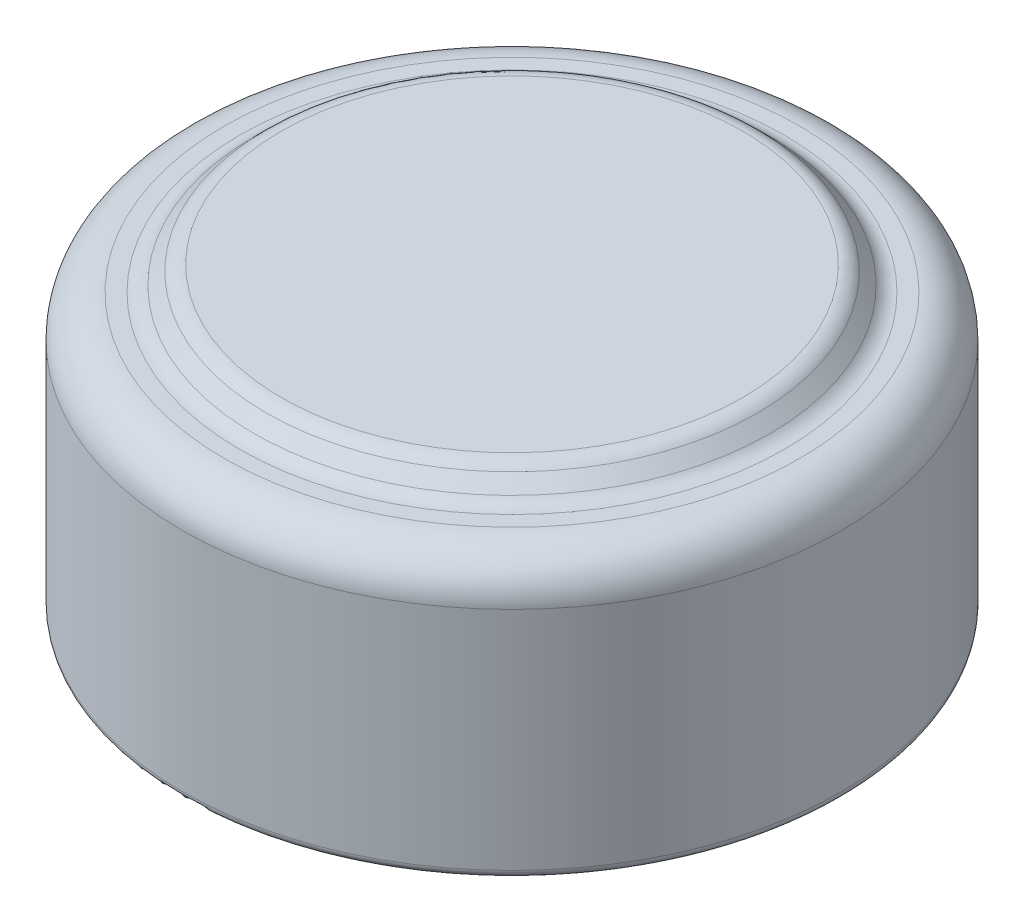
SolidWorks part; units mm, degrees
ref_plane "Front Plane" through (0, 0, 0) normal (0, 0, 1) x (1, 0, 0)
ref_plane "Top Plane" through (0, 0, 0) normal (0, 1, 0) x (1, 0, 0)
ref_plane "Right Plane" through (0, 0, 0) normal (1, 0, 0) x (0, 0, -1)
sketch "Sketch1" plane through (0, 0, 0) normal (0, 0, 1) x (1, 0, 0)
  line L0 (0, 0) -> (-3.85, 0)
  line L1 (-3.95, 0.1) -> (-3.95, 2.81)
  line L2 (0, 3.6) -> (-2.7664, 3.6)
  line L3 (0, 3.6) -> (0, 0)
  line L5 (-3.0868, 3.3832) -> (-2.9432, 3.5268)
  line L7 (-3.45, 3.31) -> (-3.2636, 3.31)
  arc A0 (-3.95, 2.81) -> (-3.45, 3.31) centre (-3.45, 2.81) cw
  arc A1 (-3.2636, 3.31) -> (-3.0868, 3.3832) centre (-3.2636, 3.56) ccw
  arc A2 (-2.7664, 3.6) -> (-2.9432, 3.5268) centre (-2.7664, 3.35) ccw
  arc A3 (-3.85, 0) -> (-3.95, 0.1) centre (-3.85, 0.1) cw
  point P9 (-3.95, 3.31)
  point P12 (-3.16, 3.31)
  point P17 (-3.95, 0)
  dimension "D6" = 0.5
  dimension "D7" = 0.25
  dimension "D8" = 0.1
  dimension "D5" = 45
  dimension "D1" = 3.95
  dimension "D2" = 3.6
  dimension "D3" = 3.16
  dimension "D4" = 3.31
revolve "Revolve1" add sketch "Sketch1" angle 360 about L3
sketch "Sketch2" plane through (0, 0, 0) normal (0, -1, 0) x (1, 0, 0)
  line L0 (0.25, -0.25) -> (0.25, -1.5)
  line L1 (-0.25, -0.25) -> (-0.25, -1.5)
  line L2 (-0.25, 1.5) -> (0.25, 1.5)
  line L3 (-0.25, 1.5) -> (-0.25, 0.25)
  line L4 (-0.25, -1.5) -> (0.25, -1.5)
  line L5 (0.25, 1.5) -> (0.25, 0.25)
  line L6 (-1.5, 0.25) -> (-0.25, 0.25)
  line L7 (-1.5, 0.25) -> (-1.5, -0.25)
  line L8 (-1.5, -0.25) -> (-0.25, -0.25)
  line L9 (1.5, 0.25) -> (1.5, -0.25)
  line L10 (0.25, 0.25) -> (1.5, 0.25)
  line L11 (0.25, -0.25) -> (1.5, -0.25)
  circle A0 centre (0, 0) radius 2.5 construction
  text T0 "                     SR41" font "Century Gothic" height 1
  dimension "D1" = 5
  dimension "D2" = 3
  dimension "D3" = 3
  dimension "D4" = 1.5
  dimension "D5" = 1.5
  dimension "D6" = 0.5
  dimension "D7" = 0.5
  dimension "D8" = 0.25
  dimension "D9" = 0.25
wrap "Wrap1" sketch "Sketch2" wrap type scribe source sketch "Sketch2" face at (-3.85, 0, 0)
